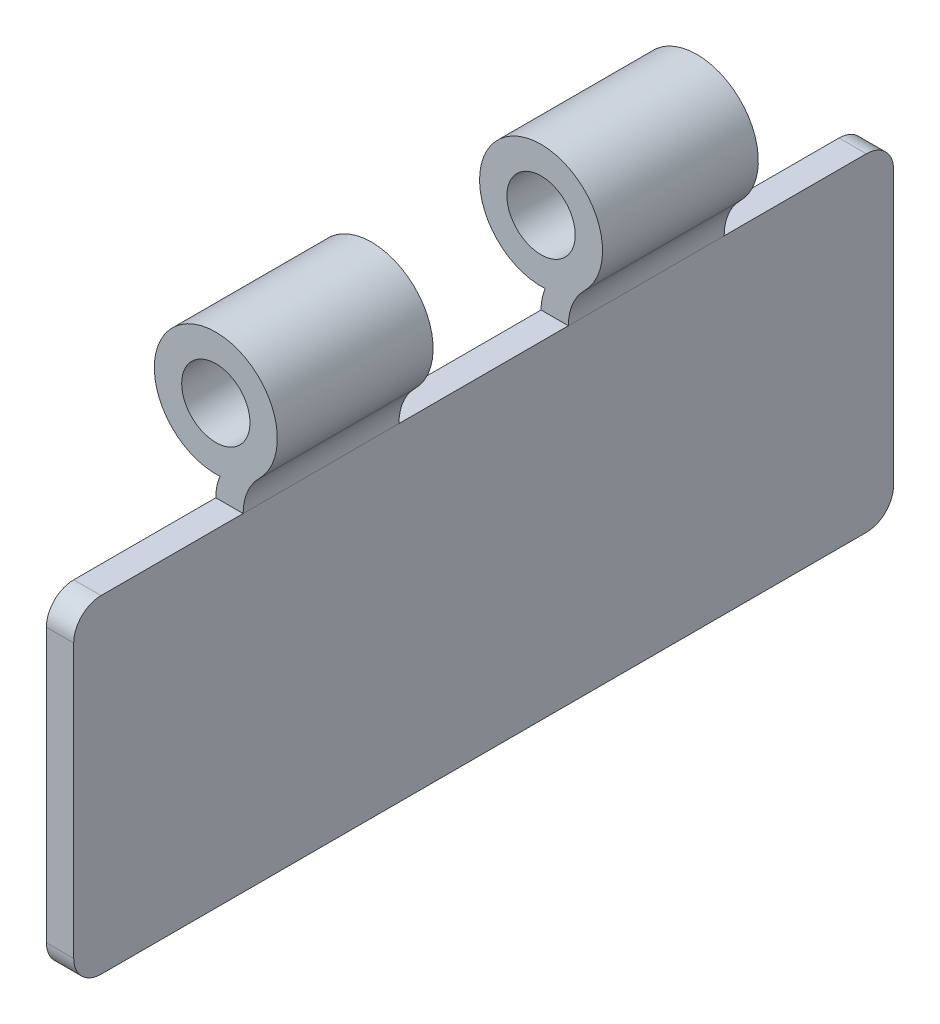
SolidWorks part; units mm, degrees
ref_plane "Front Plane" through (0, 0, 0) normal (0, 0, 1) x (1, 0, 0)
ref_plane "Top Plane" through (0, 0, 0) normal (0, 1, 0) x (1, 0, 0)
ref_plane "Right Plane" through (0, 0, 0) normal (1, 0, 0) x (0, 0, -1)
sketch "Sketch1" plane through (0, 0, 0) normal (0, 0, 1) x (1, 0, 0)
  line L0 (2.54, 0) -> (-2.54, 0)
  line L1 (-2.54, 0) -> (-2.54, 30.48)
  line L2 (0, 0) -> (0, 30.48)
  line L3 (2.54, 0) -> (2.54, 30.48)
  line L4 (2.54, 30.48) -> (0, 30.48)
  circle A0 centre (0, 38.1) radius 5.715
  arc A1 (-2.54, 30.48) -> (-4.0242, 34.042) centre (-7.5565, 30.48) ccw
  arc A2 (0, 30.48) -> (-0.381, 32.3977) centre (-5.0165, 30.48) ccw
  circle A3 centre (0, 38.1) radius 3.175
  arc A4 (2.54, 30.48) -> (4.0242, 34.042) centre (7.5565, 30.48) cw
  arc A5 (0, 30.48) -> (0.381, 32.3977) centre (5.0165, 30.48) cw
  dimension "D1" = 11.43
  dimension "D4" = 7.62
  dimension "D5" = 6.35
  dimension "D2" = 2.54
  dimension "D3" = 38.1
extrude "Boss-Extrude1" add sketch "Sketch1" along normal mid plane 76.2 contours A0 A3 | A5 L4 A4 A0 | L3 L4 L2 L0 region at (1.27, 15.24, 0) region at (1.5794, 31.6633, 0) region at (2.2845, 33.0383, 0)
extrude "Cut-Extrude1" cut sketch "Sketch1<3>" against normal mid plane 15.748 contours A0 A3 | A5 L4 A4 A0 region at (1.5794, 31.6633, 0) region at (2.2845, 33.0383, 0)
sketch "Sketch1<3>" plane through (0, 0, 0) normal (0, 0, 1) x (1, 0, 0) same geometry as "Sketch1"
sketch "Sketch2" plane through (0, 0, 38.1) normal (0, 0, 1) x (1, 0, 0)
  line L0 (2.54, 30.48) -> (0, 30.48)
  arc A0 (4.0242, 34.042) -> (2.54, 30.48) centre (7.5565, 30.48) ccw construction
  arc A1 (0.381, 32.3977) -> (0, 30.48) centre (5.0165, 30.48) ccw construction
  circle A2 centre (0, 38.1) radius 3.175 construction
  arc A3 (4.0242, 34.042) -> (0.381, 32.3977) centre (0, 38.1) ccw construction
  arc A4 (4.0242, 34.042) -> (2.54, 30.48) centre (7.5565, 30.48) ccw
  arc A5 (0.381, 32.3977) -> (0, 30.48) centre (5.0165, 30.48) ccw
  circle A6 centre (0, 38.1) radius 3.175
  arc A7 (4.0242, 34.042) -> (0.381, 32.3977) centre (0, 38.1) ccw
extrude "Cut-Extrude2" cut sketch "Sketch2" against normal blind 15.748
mirror "Mirror1" about plane through (0, 0, 0) normal (0, 0, 1) of "Cut-Extrude2"
fillet "Fillet1" radius 2.54 4 edges at (1.27, 0, 38.1) (1.27, 30.48, 38.1) (1.27, 0, -38.1) (1.27, 30.48, -38.1)
